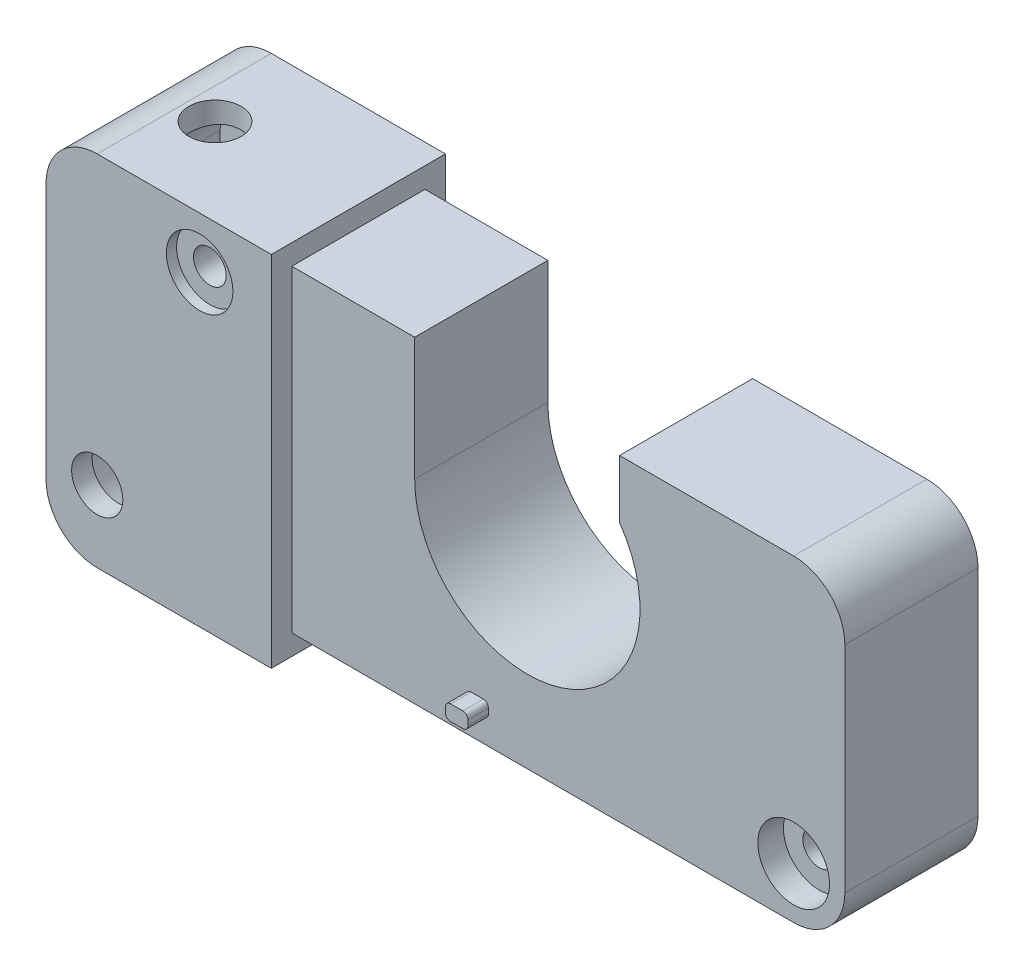
SolidWorks part; units mm, degrees
ref_plane "Front Plane" through (0, 0, 0) normal (0, 0, 1) x (1, 0, 0)
ref_plane "Top Plane" through (0, 0, 0) normal (0, 1, 0) x (1, 0, 0)
ref_plane "Right Plane" through (0, 0, 0) normal (1, 0, 0) x (0, 0, -1)
sketch "Sketch1" plane through (0, 0, 0) normal (0, 0, 1) x (1, 0, 0)
  line L0 (0, 21) -> (78, 21) construction
  line L1 (5, 0) -> (73, 0)
  line L2 (0, 5) -> (0, 30)
  line L3 (5, 35) -> (73, 35)
  line L4 (78, 5) -> (78, 30)
  line L5 (45, 35) -> (45, 0) construction
  line L6 (34, 21) -> (34, 35)
  line L7 (54, 35) -> (54, 27.3246)
  line L11 (22, 35) -> (22, 0) construction
  arc A0 (34, 21) -> (54, 27.3246) centre (45, 21) ccw
  arc A1 (5, 0) -> (0, 5) centre (5, 5) cw
  arc A2 (0, 30) -> (5, 35) centre (5, 30) cw
  arc A3 (73, 0) -> (78, 5) centre (73, 5) ccw
  arc A4 (78, 30) -> (73, 35) centre (73, 30) ccw
  point P18 (0, 0)
  point P21 (0, 35)
  point P24 (78, 0)
  dimension "D5" = 22
  dimension "D8" = 5
  dimension "D1" = 35
  dimension "D2" = 34
  dimension "D3" = 21
  dimension "D4" = 24
  dimension "D6" = 20
  dimension "D7" = 12
extrude "Boss-Extrude1" add sketch "Sketch1" along normal blind 17 contours L4 A4 L3 L7 A0 L6 A2 L2 A1 L1 A3 region at (2.069, 2.069, 0)
sketch "Sketch3" plane through (0, 0, 17) normal (0, 0, 1) x (1, 0, 0)
  line L0 (78, 5) -> (78, 30) construction
  line L1 (71, 33) -> (21, 33)
  line L2 (76, 28) -> (76, 7)
  line L3 (71, 2) -> (21, 2)
  line L4 (21, 33) -> (21, 2)
  line L6 (5, 0) -> (73, 0) construction
  line L7 (54, 35) -> (73, 35) construction
  line L8 (34, 21) -> (34, 35) construction
  line L9 (5, 35) -> (34, 35) construction
  line L10 (22, 35) -> (78, 35)
  line L11 (22, 35) -> (22, 0)
  line L12 (22, 0) -> (78, 0)
  line L13 (78, 35) -> (78, 0)
  arc A0 (71, 2) -> (76, 7) centre (71, 7) ccw
  arc A1 (76, 28) -> (71, 33) centre (71, 28) ccw
  line M9 (78, 5) -> (78, 30)
  arc M10 (78, 30) -> (73, 35) centre (73, 30) ccw
  line M11 (73, 35) -> (54, 35)
  line M12 (54, 35) -> (54, 27.3246)
  arc M13 (54, 27.3246) -> (34, 21) centre (45, 21) cw
  line M14 (34, 21) -> (34, 35)
  line M15 (34, 35) -> (5, 35)
  line M19 (5, 0) -> (73, 0)
  arc M20 (73, 0) -> (78, 5) centre (73, 5) ccw
  dimension "D5" = 5
  dimension "D1" = 2
  dimension "D2" = 2
  dimension "D3" = 2
  dimension "D4" = 13
  dimension "D6" = 2
  dimension "D7" = 2
  dimension "D8" = 12
extrude "Cut-Extrude1" cut sketch "Sketch3" against normal blind 17 contours L11 L1 M15 M14 | A1 L2 A0 L3 L11 L1 M19 M20 M9 M10 M11 M12 region at (62.5, 33.6604, 17) region at (28, 34, 17)
extrude "Cut-Extrude2" cut sketch "Sketch3<3>" against normal blind 2 contours L2 A1 L1 L4 L3 A0 M12 M13 M14 region at (74.0952, 31.0952, 17)
sketch "Sketch3<3>" plane through (0, 0, 17) normal (0, 0, 1) x (1, 0, 0) same geometry as "Sketch3"
sketch "Sketch5" plane through (0, 0, 0) normal (0, 0, -1) x (-1, 0, 0)
  line L1 (-22, 33) -> (-82, 33)
  line L2 (-22, 33) -> (-22, -2)
  line L3 (-22, -2) -> (-82, -2)
  line L4 (-82, 33) -> (-82, -2)
  dimension "D1" = 60
  dimension "D2" = 35
extrude "Cut-Extrude3" cut sketch "Sketch5" against normal blind 2
ref_plane "Plane1" through (0, 0, 14) normal (0, 0, 1) x (1, 0, 0)
sketch "Sketch6" plane through (0, 0, 14) normal (0, 0, 1) x (1, 0, 0)
  line L0 (22, 35) -> (22, 0) construction
  line L1 (22, 32) -> (69.5, 32)
  line L2 (22, 32) -> (22, 3)
  line L3 (22, 3) -> (69.5, 3)
  line L4 (74.5, 27) -> (74.5, 8)
  line L5 (76, 28) -> (76, 7) construction
  line L6 (71, 2) -> (22, 2) construction
  line L7 (71, 33) -> (54, 33) construction
  arc A0 (69.5, 3) -> (74.5, 8) centre (69.5, 8) ccw
  arc A1 (74.5, 27) -> (69.5, 32) centre (69.5, 27) ccw
  dimension "D4" = 5
  dimension "D1" = 1.5
  dimension "D2" = 1
  dimension "D3" = 1
extrude "Cut-Extrude4" cut sketch "Sketch6" against normal blind 11
sketch "Sketch11" plane through (0, 0, 15) normal (0, 0, 1) x (1, 0, 0)
  line L0 (0, 5) -> (0, 30) construction
  line L1 (22, 2) -> (7, 2)
  line L2 (22, 2) -> (22, 33)
  line L3 (22, 33) -> (7, 33)
  line L4 (2, 7) -> (2, 28)
  arc A0 (7, 2) -> (2, 7) centre (7, 7) cw
  arc A1 (7, 33) -> (2, 28) centre (7, 28) ccw
  dimension "D3" = 5
  dimension "D1" = 2
  dimension "D2" = 31
extrude "Cut-Extrude11" cut sketch "Sketch11" against normal blind 13
sketch "Sketch12" plane through (0, 0, 15) normal (0, 0, 1) x (1, 0, 0)
  line L0 (22, 33) -> (22, 2) construction
  line L1 (39.5, 5.75) -> (40.7, 5.75)
  line L2 (39, 5.25) -> (39, 4.75)
  line L3 (39.5, 4.25) -> (40.7, 4.25)
  line L4 (41.2, 5.25) -> (41.2, 4.75)
  line L7 (5, 0) -> (22, 0) construction
  arc A0 (41.2, 4.75) -> (40.7, 4.25) centre (40.7, 4.75) cw
  arc A1 (41.2, 5.25) -> (40.7, 5.75) centre (40.7, 5.25) ccw
  arc A2 (39, 4.75) -> (39.5, 4.25) centre (39.5, 4.75) ccw
  arc A3 (39, 5.25) -> (39.5, 5.75) centre (39.5, 5.25) cw
  point P10 (41.2, 4.25)
  point P15 (39, 4.25)
  point P18 (39, 5.75)
  dimension "D5" = 0.5
  dimension "D1" = 2.2
  dimension "D2" = 1.5
  dimension "D3" = 17
  dimension "D4" = 5.75
extrude "Boss-Extrude2" add sketch "Sketch12" along normal blind 2
sketch "Sketch13" plane through (0, 0, 17) normal (0, 0, 1) x (1, 0, 0)
  line L0 (5, 35) -> (5, 0) construction
  line L1 (5, 35) -> (22, 35) construction
  line L2 (5, 0) -> (22, 0) construction
  line L3 (0, 5) -> (0, 30) construction
  line L4 (0, 7) -> (22, 7) construction
  line L5 (22, 33) -> (22, 2) construction
  circle A0 centre (5, 7) radius 2.5
  dimension "D1" = 5
  dimension "D2" = 5
  dimension "D3" = 28
extrude "Cut-Extrude12" cut sketch "Sketch13" against normal blind 5
sketch "Sketch14" plane through (0, 35, 0) normal (0, 1, 0) x (1, 0, 0)
  line L0 (5, -8.5) -> (22, -8.5) construction
  line L1 (5, -17) -> (5, 0) construction
  line L2 (22, -2) -> (22, -15) construction
  line L3 (8, 0) -> (8, -17) construction
  line L6 (5, 0) -> (22, 0) construction
  line L7 (5, -17) -> (22, -17) construction
  line L8 (0, -17) -> (0, 0) construction
  circle A1 centre (8, -8.5) radius 2.55
  dimension "D2" = 5.1
  dimension "D1" = 8
extrude "Cut-Extrude14" cut sketch "Sketch14" against normal blind 15
sketch "Sketch15" plane through (0, 0, 17) normal (0, 0, 1) x (1, 0, 0)
  line L0 (15, 35) -> (15, 0) construction
  line L1 (5, 35) -> (22, 35) construction
  line L2 (5, 0) -> (22, 0) construction
  line L3 (0, 30) -> (22, 30) construction
  line L4 (0, 5) -> (0, 30) construction
  line L5 (22, 33) -> (22, 2) construction
  circle A0 centre (15, 30) radius 3.25
  circle A1 centre (15, 30) radius 1.6
  dimension "D3" = 6.5
  dimension "D4" = 3.2
  dimension "D1" = 15
  dimension "D2" = 5
extrude "Boss-Extrude5" add sketch "Sketch15" against normal through all
extrude "Cut-Extrude16" cut sketch "Sketch15<4>" against normal blind 1
sketch "Sketch15<4>" plane through (0, 0, 17) normal (0, 0, 1) x (1, 0, 0) same geometry as "Sketch15"
sketch "Sketch18" plane through (0, 0, 17) normal (0, 0, 1) x (1, 0, 0)
  circle A0 centre (15, 30) radius 1.6
  dimension "D1" = 3.2
extrude "Cut-Extrude17" cut sketch "Sketch18" against normal blind 15
sketch "Sketch20" plane through (0, 0, 15) normal (0, 0, 1) x (1, 0, 0)
  line L0 (71, 33) -> (71, 2) construction
  line L1 (71, 33) -> (54, 33) construction
  line L2 (71, 2) -> (22, 2) construction
  line L3 (76, 7) -> (22, 7) construction
  line L4 (22, 33) -> (22, 2) construction
  line L5 (76, 28) -> (76, 7) construction
  arc A0 (71, 2) -> (76, 7) centre (71, 7) ccw construction
  circle A1 centre (71, 7) radius 4.5
  circle A2 centre (71, 7) radius 1.6
  dimension "D3" = 9
  dimension "D4" = 3.2
  dimension "D1" = 5
  dimension "D2" = 5
extrude "Boss-Extrude6" add sketch "Sketch20" against normal blind 13
extrude "Cut-Extrude20" cut sketch "Sketch20<3>" against normal through all from surface contours A2 starting at face at (52.0388, 20.5674, 15)
sketch "Sketch20<3>" plane through (0, 0, 15) normal (0, 0, 1) x (1, 0, 0) same geometry as "Sketch20"
sketch "Sketch21" plane through (0, 0, 2) normal (0, 0, -1) x (-1, 0, 0)
  circle A0 centre (-71, 7) radius 3.5
  dimension "D1" = 7
ref_plane "Plane13" through (0, 0, 8.5) normal (0, 0, 1) x (1, 0, 0)
sketch "Sketch22" plane through (22, 0, 0) normal (1, 0, 0) x (0, 0, -1)
  line L0 (-2, 2) -> (-15, 2) construction
  line L1 (-15, 33) -> (-2, 33)
  line L2 (-15, 33) -> (-15, 2)
  line L3 (-15, 2) -> (-2, 2)
  line L4 (-2, 33) -> (-2, 2)
  line L5 (-2, 2) -> (-15, 2) construction
  line L6 (-14, 17.05) -> (-14, -17.05) construction
  line L11 (-14, 32) -> (-3, 32)
  line L12 (-14, 32) -> (-14, 3)
  line L13 (-14, 3) -> (-3, 3)
  line L14 (-3, 32) -> (-3, 3)
  line L15 (0, 35) -> (0, 0) construction
  dimension "D1" = 2
  dimension "D2" = 1
  dimension "D3" = 1
  dimension "D4" = 1
extrude "Boss-Extrude7" add sketch "Sketch22" against normal blind 3
sketch "Sketch24" plane through (0, 0, 8.5) normal (0, 0, 1) x (1, 0, 0)
  line L1 (0, 0) -> (80, 0)
  line L2 (0, 0) -> (0, 36)
  line L3 (0, 36) -> (80, 36)
  line L4 (80, 0) -> (80, 36)
  dimension "D1" = 36
  dimension "D2" = 80
extrude "Cut-Extrude21" cut sketch "Sketch21" against normal blind 2
sketch "Sketch29" plane through (0, 0, 15) normal (0, 0, 1) x (1, 0, 0)
  circle A0 centre (71, 7) radius 3.5
  dimension "D1" = 7
extrude "Cut-Extrude22" cut sketch "Sketch29" against normal blind 2.5
sketch "Sketch36" plane through (0, 0, 15) normal (0, 0, 1) x (1, 0, 0)
  line L0 (34, 33) -> (34, 21)
  line L1 (54, 27.3246) -> (54, 33)
  line L2 (54, 33) -> (54.7, 33)
  line L3 (71, 33) -> (54, 33) construction
  line L4 (54.7, 33) -> (54.7, 27.3246)
  line L5 (33.3, 21) -> (33.3, 33)
  line L6 (34, 33) -> (22, 33) construction
  line L7 (33.3, 33) -> (34, 33)
  line L15 (76, 7) -> (76, 28)
  line L16 (71, 33) -> (54, 33)
  line L17 (54, 33) -> (54, 27.3246)
  line L18 (34, 21) -> (34, 33)
  line L19 (34, 33) -> (22, 33)
  line L20 (22, 33) -> (22, 2)
  line L21 (22, 2) -> (71, 2)
  line L23 (54.7, 33) -> (54, 33)
  line L24 (54, 33) -> (54, 27.3246)
  line L25 (34, 21) -> (34, 33)
  line L26 (34, 33) -> (33.3, 33)
  arc A2 (33.3, 21) -> (54.7, 27.3246) centre (44.998, 20.7853) ccw
  arc A4 (34, 21) -> (54, 27.3246) centre (45, 21) ccw
  arc A7 (76, 28) -> (71, 33) centre (71, 28) ccw
  arc A8 (34, 21) -> (54, 27.3246) centre (45, 21) ccw
  arc A9 (71, 2) -> (76, 7) centre (71, 7) ccw
  line M9 (71, 33) -> (54, 33)
  line M10 (54, 33) -> (54, 27.3246)
  arc M11 (54, 27.3246) -> (34, 21) centre (45, 21) cw
  line M12 (34, 21) -> (34, 33)
  line M13 (34, 33) -> (22, 33)
  dimension "D3" = 11.7
  dimension "D1" = 0.7
  dimension "D2" = 0.7
  dimension "D4" = 0
extrude "Boss-Extrude10" add sketch "Sketch36" against normal up to surface (13 mm away) contours L5 A2 L4 M9 M10 M11 M12 M13 region at (33.6654, 27, 15) up to face at (67.5, 7, 2)
